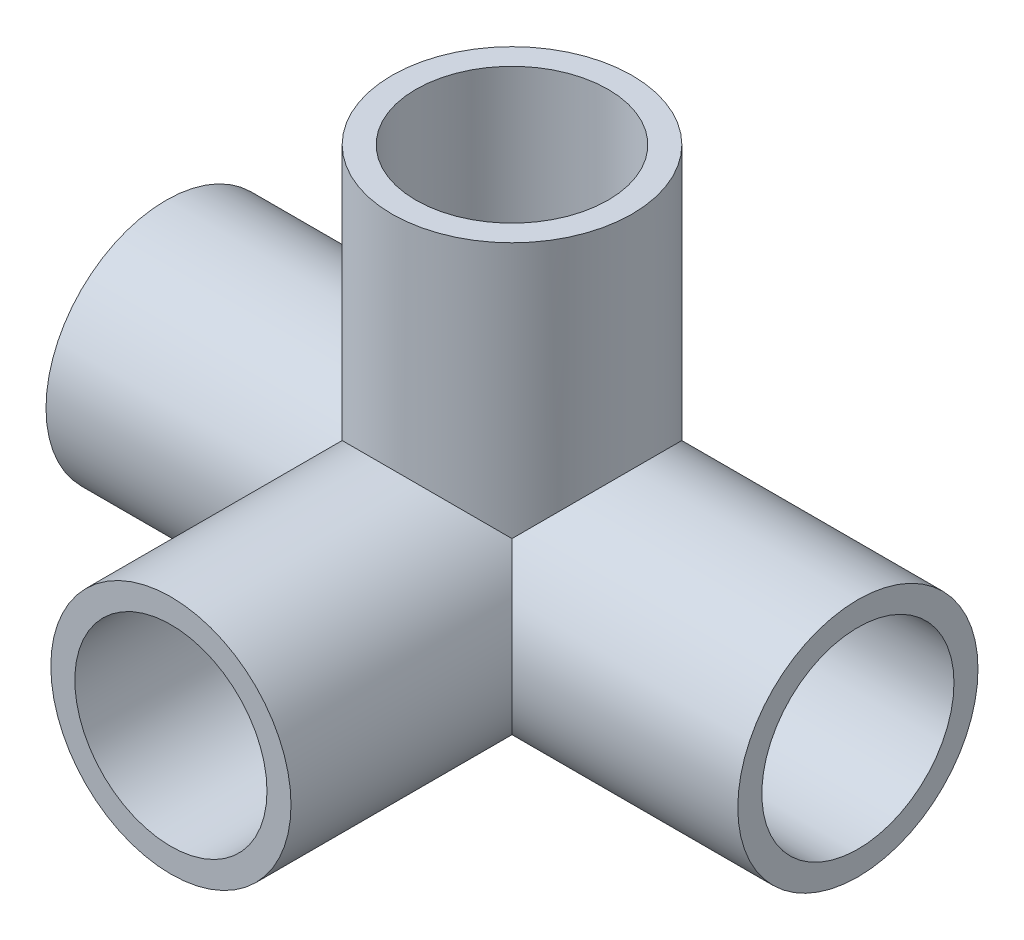
SolidWorks part; units mm, degrees
ref_plane "前视基准面" through (0, 0, 0) normal (0, 0, 1) x (1, 0, 0)
ref_plane "上视基准面" through (0, 0, 0) normal (0, 1, 0) x (1, 0, 0)
ref_plane "右视基准面" through (0, 0, 0) normal (1, 0, 0) x (0, 0, -1)
sketch "草图1" plane through (0, 0, 0) normal (1, 0, 0) x (0, 0, -1)
  circle A1 centre (0, 0) radius 10
  dimension "D2" = 20
extrude "凸台-拉伸1" add sketch "草图1" along normal mid plane 72
sketch "草图2" plane through (0, 0, 0) normal (0, 1, 0) x (1, 0, 0)
  circle A1 centre (0, 0) radius 10
  dimension "D2" = 20
extrude "凸台-拉伸2" add sketch "草图2" along normal blind 35.5
sketch "草图3" plane through (0, 0, 0) normal (0, 0, 1) x (1, 0, 0)
  circle A1 centre (0, 0) radius 10
  dimension "D2" = 20
extrude "凸台-拉伸3" add sketch "草图3" along normal blind 35.5
shell "抽壳1" thickness 2.5 removed face at (-36, 0, -10) removed face at (36, 0, -10) removed face at (10, 0, 35.5) removed face at (0, 35.5, 10) outward yes
